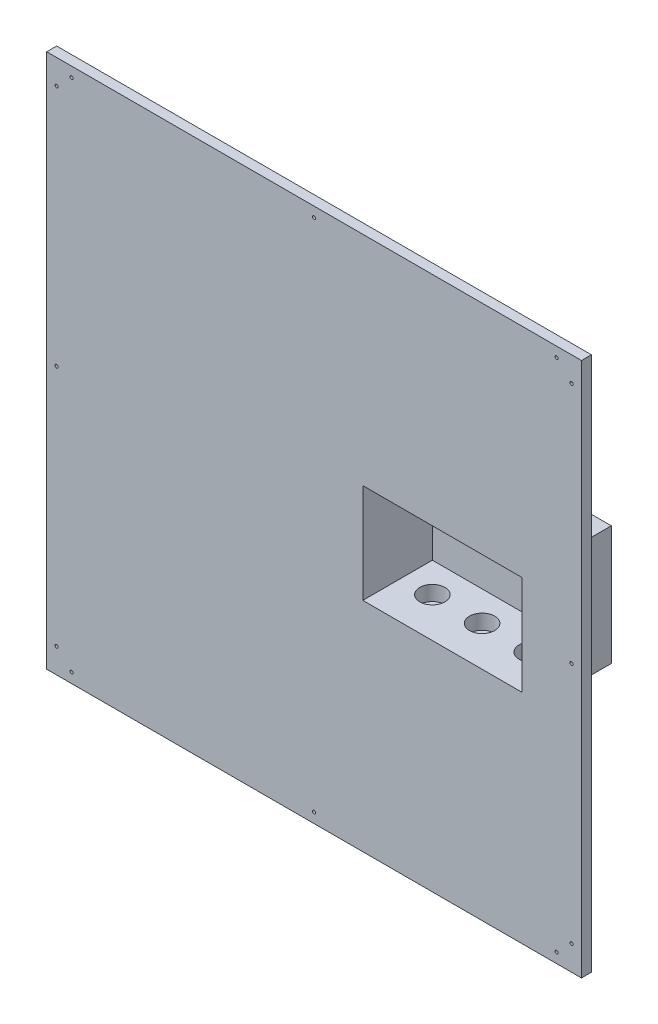
SolidWorks part; units mm, degrees
material "PE High Density Film"
ref_plane "Front Plane" through (0, 0, 0) normal (0, 0, 1) x (1, 0, 0)
ref_plane "Top Plane" through (0, 0, 0) normal (0, 1, 0) x (1, 0, 0)
ref_plane "Right Plane" through (0, 0, 0) normal (1, 0, 0) x (0, 0, -1)
sketch "Sketch1" plane through (0, 0, 0) normal (0, 0, 1) x (1, 0, 0)
  line L1 (0, 0) -> (683.26, 0)
  line L2 (0, 0) -> (0, 683.26)
  line L3 (0, 683.26) -> (683.26, 683.26)
  line L4 (683.26, 0) -> (683.26, 683.26)
  line L5 (403.86, 405.13) -> (607.06, 405.13)
  line L6 (403.86, 405.13) -> (403.86, 278.13)
  line L7 (403.86, 278.13) -> (607.06, 278.13)
  line L8 (607.06, 405.13) -> (607.06, 278.13)
  point P9 (607.06, 341.63)
  dimension "D1" = 683.26
  dimension "D2" = 76.2
  dimension "D3" = 341.63
  dimension "D4" = 127
  dimension "D5" = 203.2
extrude "Boss-Extrude1" add sketch "Sketch1" along normal blind 12.7
sketch "Sketch2" plane through (0, 278.13, 0) normal (0, 1, 0) x (1, 0, 0)
  line L1 (403.86, 0) -> (607.06, 0)
  line L2 (403.86, 0) -> (403.86, 76.2)
  line L3 (403.86, 76.2) -> (607.06, 76.2)
  line L4 (607.06, 0) -> (607.06, 76.2)
  dimension "D1" = 76.2
extrude "Boss-Extrude2" add sketch "Sketch2" against normal blind 25.4
sketch "Sketch3" plane through (0, 278.13, 0) normal (0, 1, 0) x (1, 0, 0)
  line L4 (607.06, 0) -> (607.06, 76.2)
  line L6 (607.06, -12.7) -> (607.06, 0)
  line L9 (607.06, 0) -> (607.06, 76.2)
  line L10 (403.86, 0) -> (403.86, -12.7)
  line L11 (403.86, -12.7) -> (607.06, -12.7)
  line L12 (607.06, -12.7) -> (607.06, 0)
  line L16 (403.86, 0) -> (403.86, -12.7)
  line L17 (403.86, -12.7) -> (607.06, -12.7)
  line L18 (607.06, 76.2) -> (403.86, 76.2)
  line L19 (607.06, 76.2) -> (403.86, 76.2)
  line L20 (403.86, 76.2) -> (403.86, 0)
  line L21 (403.86, 76.2) -> (403.86, 0)
  circle A1 centre (441.96, 38.1) radius 16.0655
  circle A2 centre (505.46, 38.1) radius 16.0655
  circle A3 centre (568.96, 38.1) radius 16.0655
  dimension "D2" = 32.131
  dimension "D4" = 32.131
  dimension "D5" = 32.131
  dimension "D6" = 63.5
  dimension "D7" = 63.5
  dimension "D1" = 0
extrude "Cut-Extrude1" cut sketch "Sketch3" against normal blind 19.05 contours A3 | A2 | A1 region at (441.96, 278.13, -38.1) region at (505.46, 278.13, -38.1) region at (568.96, 278.13, -38.1)
sketch "Sketch4" plane through (0, 0, 0) normal (0, 0, -1) x (-1, 0, 0)
  line L0 (-607.06, 278.13) -> (-403.86, 278.13) construction
  line L1 (-607.06, 278.13) -> (-619.76, 278.13)
  line L2 (-607.06, 278.13) -> (-607.06, 405.13)
  line L3 (-607.06, 405.13) -> (-619.76, 405.13)
  line L4 (-619.76, 278.13) -> (-619.76, 405.13)
  line L5 (-607.06, 405.13) -> (-403.86, 405.13)
  line L6 (-607.06, 405.13) -> (-607.06, 417.83)
  line L7 (-607.06, 417.83) -> (-403.86, 417.83)
  line L8 (-403.86, 405.13) -> (-403.86, 417.83)
  line L9 (-403.86, 405.13) -> (-391.16, 405.13)
  line L10 (-403.86, 405.13) -> (-403.86, 278.13)
  line L11 (-403.86, 278.13) -> (-391.16, 278.13)
  line L12 (-391.16, 405.13) -> (-391.16, 278.13)
  line L13 (-403.86, 405.13) -> (-403.86, 278.13) construction
  line L15 (-607.06, 405.13) -> (-403.86, 405.13) construction
  line L16 (-607.06, 405.13) -> (-619.76, 405.13)
  line L17 (-607.06, 405.13) -> (-607.06, 417.83)
  line L18 (-607.06, 417.83) -> (-619.76, 417.83)
  line L19 (-619.76, 405.13) -> (-619.76, 417.83)
  line L20 (-403.86, 405.13) -> (-391.16, 405.13)
  line L21 (-403.86, 405.13) -> (-403.86, 417.83)
  line L22 (-403.86, 417.83) -> (-391.16, 417.83)
  line L23 (-391.16, 405.13) -> (-391.16, 417.83)
  line L24 (-607.06, 278.13) -> (-619.76, 278.13)
  line L25 (-607.06, 278.13) -> (-607.06, 265.43)
  line L26 (-607.06, 265.43) -> (-619.76, 265.43)
  line L27 (-619.76, 278.13) -> (-619.76, 265.43)
  line L28 (-403.86, 278.13) -> (-391.16, 278.13)
  line L29 (-403.86, 278.13) -> (-403.86, 265.43)
  line L30 (-403.86, 265.43) -> (-391.16, 265.43)
  line L31 (-391.16, 278.13) -> (-391.16, 265.43)
  line M7 (-403.86, 278.13) -> (-403.86, 252.73)
  line M9 (-607.06, 252.73) -> (-607.06, 278.13)
  line M10 (-607.06, 278.13) -> (-607.06, 405.13)
  line M11 (-607.06, 405.13) -> (-403.86, 405.13)
  line M12 (-403.86, 405.13) -> (-403.86, 278.13)
  dimension "D1" = 12.7
  dimension "D2" = 12.7
  dimension "D3" = 12.7
extrude "Boss-Extrude4" add sketch "Sketch4" along normal up to surface (76.2 mm away) contours L1 L27 L26 M9 | L4 L1 L3 M10 | L8 L7 L6 M11 | L19 L3 L6 L18 | L9 L23 L22 L8 | L12 L9 L11 M12 | L31 L11 L30 M7 region at (613.41, 271.78, 0) region at (613.41, 341.63, 0) region at (505.46, 411.48, 0) region at (613.41, 411.48, 0) region at (397.51, 411.48, 0) region at (397.51, 341.63, 0) region at (397.51, 271.78, 0) up to face at (505.46, 265.43, -76.2)
sketch "Sketch5" plane through (0, 0, -76.2) normal (0, 0, -1) x (-1, 0, 0)
  line L4 (-607.06, 252.73) -> (-403.86, 252.73)
  line L5 (-391.16, 265.43) -> (-391.16, 417.83)
  line L6 (-391.16, 417.83) -> (-619.76, 417.83)
  line L7 (-619.76, 417.83) -> (-619.76, 265.43)
  line L8 (-607.06, 252.73) -> (-403.86, 252.73)
  line L9 (-391.16, 265.43) -> (-391.16, 417.83)
  line L10 (-391.16, 417.83) -> (-619.76, 417.83)
  line L11 (-619.76, 417.83) -> (-619.76, 265.43)
  line L16 (-403.86, 252.73) -> (-403.86, 265.43)
  line L17 (-403.86, 252.73) -> (-403.86, 265.43)
  line L18 (-403.86, 265.43) -> (-391.16, 265.43)
  line L19 (-403.86, 265.43) -> (-391.16, 265.43)
  line L20 (-619.76, 265.43) -> (-607.06, 265.43)
  line L21 (-619.76, 265.43) -> (-607.06, 265.43)
  line L22 (-607.06, 265.43) -> (-607.06, 252.73)
  line L23 (-607.06, 265.43) -> (-607.06, 252.73)
  dimension "D1" = 0
extrude "Boss-Extrude5" add sketch "Sketch5" along normal blind 12.7
sketch "Sketch6" plane through (0, 0, 12.7) normal (0, 0, 1) x (1, 0, 0)
  line L0 (683.26, 683.26) -> (0, 683.26) construction
  line L1 (0, 683.26) -> (0, 0) construction
  line L2 (0, 0) -> (683.26, 683.26) construction
  line L3 (683.26, 683.26) -> (341.63, 341.63) construction
  line L4 (341.63, 341.63) -> (341.63, 683.26) construction
  line L6 (341.63, 341.63) -> (0, 341.63) construction
  point P0 (31.75, 670.56)
  point P5 (12.7, 651.51)
  point P20 (670.56, 651.51)
  point P21 (651.51, 670.56)
  point P22 (670.56, 31.75)
  point P23 (651.51, 12.7)
  point P24 (31.75, 12.7)
  point P25 (12.7, 31.75)
  point P26 (341.63, 670.56)
  point P29 (12.7, 341.63)
  point P32 (670.56, 341.63)
  point P33 (341.63, 12.7)
  dimension "D1" = 12.7
  dimension "D2" = 31.75
  dimension "D3" = 31.75
  dimension "D4" = 12.7
  dimension "D5" = 12.7
  dimension "D6" = 12.7
  dimension "D7" = 309.88
hole_wizard "#10-32 Tapped Hole1" positions "Sketch6" profile "Sketch7" tap size "#10-32" standard "ANSI Inch" end condition through all
sketch "Sketch7" plane through (31.75, 670.56, 12.7) normal (1, 0, 0) x (0, -1, 0)
  line L0 (0, 0) -> (0, 101.6)
  line L1 (0, 101.6) -> (2.0193, 101.6)
  line L2 (2.0193, 101.6) -> (2.0193, 0)
  line L5 (2.0193, 0) -> (0, 0)
  line L11 (0, -6.35) -> (0, 107.95) construction
  dimension "Thru Tap Drill Dia." = 4.0386
  dimension "Thru Tap Drill Depth" = 101.6
cosmetic thread "Hole Thread1" parameters "D2"=4.826
cosmetic thread "Hole Thread2" parameters "D2"=4.826
cosmetic thread "Hole Thread3" parameters "D2"=4.826
cosmetic thread "Hole Thread4" parameters "D2"=4.826
cosmetic thread "Hole Thread5" parameters "D2"=4.826
cosmetic thread "Hole Thread6" parameters "D2"=4.826
cosmetic thread "Hole Thread7" parameters "D2"=4.826
cosmetic thread "Hole Thread8" parameters "D2"=4.826
cosmetic thread "Hole Thread9" parameters "D2"=4.826
cosmetic thread "Hole Thread10" parameters "D2"=4.826
cosmetic thread "Hole Thread11" parameters "D2"=4.826
cosmetic thread "Hole Thread12" parameters "D2"=4.826
